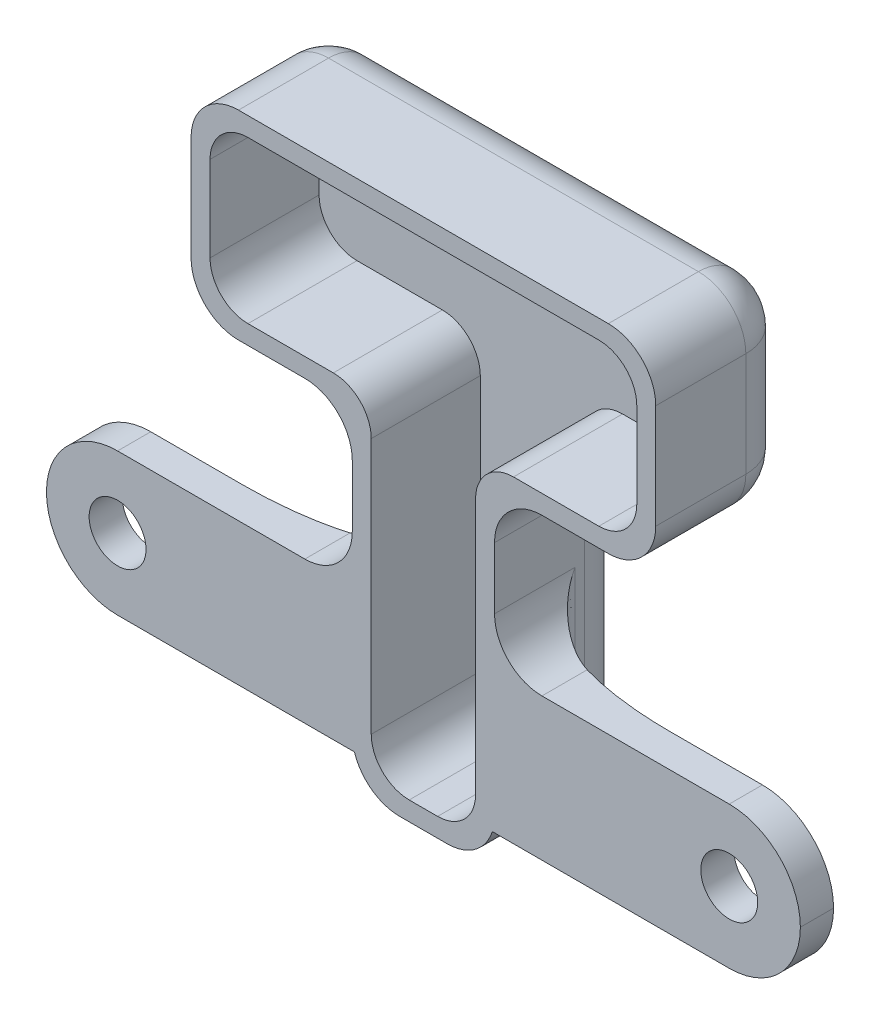
SolidWorks part; units mm, degrees
ref_plane "Front Plane" through (0, 0, 0) normal (0, 0, 1) x (1, 0, 0)
ref_plane "Top Plane" through (0, 0, 0) normal (0, 1, 0) x (1, 0, 0)
ref_plane "Right Plane" through (0, 0, 0) normal (1, 0, 0) x (0, 0, -1)
sketch "Sketch1" plane through (0, 0, 0) normal (0, 0, 1) x (1, 0, 0)
  line L0 (7.5, 35) -> (24.5, 35)
  line L2 (-7.5, 35) -> (-7.5, 0)
  line L3 (-7.5, 0) -> (7.5, 0)
  line L4 (7.5, 35) -> (7.5, 0)
  line L5 (-24.5, 56) -> (24.5, 56)
  line L6 (-24.5, 56) -> (-24.5, 35)
  line L7 (-24.5, 35) -> (-7.5, 35)
  line L8 (24.5, 56) -> (24.5, 35)
  line L9 (-7.5, 11) -> (7.5, 11) construction
  point P9 (0, 0)
  point P10 (0, 56)
  dimension "D5" = 24
  dimension "D1" = 15
  dimension "D2" = 35
  dimension "D3" = 21
  dimension "D4" = 49
extrude "Boss-Extrude1" add sketch "Sketch1" along normal blind 3
sketch "Sketch6" plane through (0, 0, 3) normal (0, 0, 1) x (1, 0, 0)
  line L0 (-22.5, 37) -> (-5.5, 37)
  line L1 (-5.5, 37) -> (-5.5, 2)
  line L2 (-5.5, 2) -> (5.5, 2)
  line L3 (5.5, 2) -> (5.5, 37)
  line L4 (5.5, 37) -> (22.5, 37)
  line L5 (22.5, 37) -> (22.5, 54)
  line L6 (22.5, 54) -> (-22.5, 54)
  line L7 (-22.5, 54) -> (-22.5, 37)
  line L8 (-24.5, 35) -> (-7.5, 35)
  line L9 (-7.5, 35) -> (-7.5, 0)
  line L10 (-7.5, 0) -> (7.5, 0)
  line L11 (7.5, 0) -> (7.5, 35)
  line L12 (7.5, 35) -> (24.5, 35)
  line L13 (24.5, 35) -> (24.5, 56)
  line L14 (24.5, 56) -> (-24.5, 56)
  line L15 (-24.5, 56) -> (-24.5, 35)
  line L16 (-24.5, 35) -> (-7.5, 35)
  line L17 (-7.5, 35) -> (-7.5, 0)
  line L18 (-7.5, 0) -> (7.5, 0)
  line L19 (7.5, 0) -> (7.5, 35)
  line L20 (7.5, 35) -> (24.5, 35)
  line L21 (24.5, 35) -> (24.5, 56)
  line L22 (24.5, 56) -> (-24.5, 56)
  line L23 (-24.5, 56) -> (-24.5, 35)
  dimension "D1" = 0
  dimension "D2" = 2
extrude "Boss-Extrude5" add sketch "Sketch6" along normal blind 11.5
sketch "Sketch7" plane through (0, 0, 14.5) normal (0, 0, -1) x (-1, 0, 0)
  line L0 (-7.5, 0) -> (-7.5, 35) construction
  line L1 (-7.5, 18.5) -> (-39.75, 18.5)
  line L2 (-7.5, 18.5) -> (-7.5, 3.5)
  line L3 (-7.5, 3.5) -> (-39.75, 3.5)
  line L4 (-39.75, 18.5) -> (-39.75, 3.5)
  line L5 (-7.5, 35) -> (-24.5, 35) construction
  line L6 (0, 59.2696) -> (0, -7.8066) construction
  line L7 (7.5, 3.5) -> (39.75, 3.5)
  line L8 (39.75, 18.5) -> (39.75, 3.5)
  line L9 (7.5, 18.5) -> (39.75, 18.5)
  line L10 (7.5, 18.5) -> (7.5, 3.5)
  circle A0 centre (-32.25, 11) radius 3
  circle A1 centre (32.25, 11) radius 3
  point P6 (-39.75, 11)
  point P14 (0, 0)
  dimension "6" = 6
  dimension "D1" = 24
  dimension "D2" = 79.5
  dimension "D3" = 15
  dimension "D4" = 64.5
extrude "Boss-Extrude6" add sketch "Sketch7" along normal blind 3.5
fillet "Fillet4" radius 4 8 edges at (-5.5, 2, 8.75) (5.5, 2, 8.75) (-5.5, 37, 8.75) (-22.5, 37, 8.75) (5.5, 37, 8.75) (22.5, 37, 8.75) (22.5, 54, 8.75) (-22.5, 54, 8.75)
fillet "Fillet5" radius 5 16 edges at (-7.5, 35, 7.25) (7.5, 35, 7.25) (-7.5, 0, 7.25) (7.5, 0, 7.25) (0, 0, 0) (7.5, 17.5, 0) (-7.5, 17.5, 0) (-16, 35, 0) (16, 35, 0) (-24.5, 45.5, 0) (24.5, 45.5, 0) (0, 56, 0) (24.5, 35, 7.25) (24.5, 56, 7.25) (-24.5, 35, 7.25) (-24.5, 56, 7.25)
fillet "Fillet6" radius 5 4 edges at (-7.4421, 4.2412, 11) (-7.5, 11.75, 11) (7.4421, 4.2412, 11) (7.5, 11.75, 11) second distance 15 first distance on face at (-6.0342, 2.5291, 10.1667) first distance on face at (-7.5, 17.8333, 10.1667) first distance on face at (6.0342, 2.5291, 10.1667) first distance on face at (7.5, 17.8333, 10.1667)
fillet "Fillet7" radius 5 2 edges
fillet "Fillet8" radius 7.5 4 edges at (-39.75, 18.5, 12.75) (-39.75, 3.5, 12.75) (39.75, 18.5, 12.75) (39.75, 3.5, 12.75)
sketch "Sketch9" plane through (0, 0, 3) normal (0, 0, 1) x (1, 0, 0)
  line L0 (-35.7203, 46) -> (44.4037, 46) construction
  line L1 (18.5, 54) -> (-18.5, 54) construction
  line L2 (0, 62.411) -> (0, -7.2535) construction
  circle A0 centre (-18.25, 46) radius 1.05
  circle A1 centre (18.25, 46) radius 1.05
  dimension "D2" = 2.1
  dimension "D1" = 8
  dimension "D3" = 36.5
extrude "Cut-Extrude2" cut sketch "Sketch9" against normal through all
sketch "Sketch10" plane through (0, 0, 0) normal (0, 0, -1) x (-1, 0, 0)
  circle A0 centre (-18.25, 46) radius 1.75
  circle A1 centre (18.25, 46) radius 1.75
  dimension "D1" = 3.5
  dimension "D2" = 3.5
extrude "Cut-Extrude3" cut sketch "Sketch10" against normal blind 1.5
equation "\"D2@Sketch7\"=64.5+15"
equation "\"D2@Sketch10\"=\"D1@Sketch10\""
